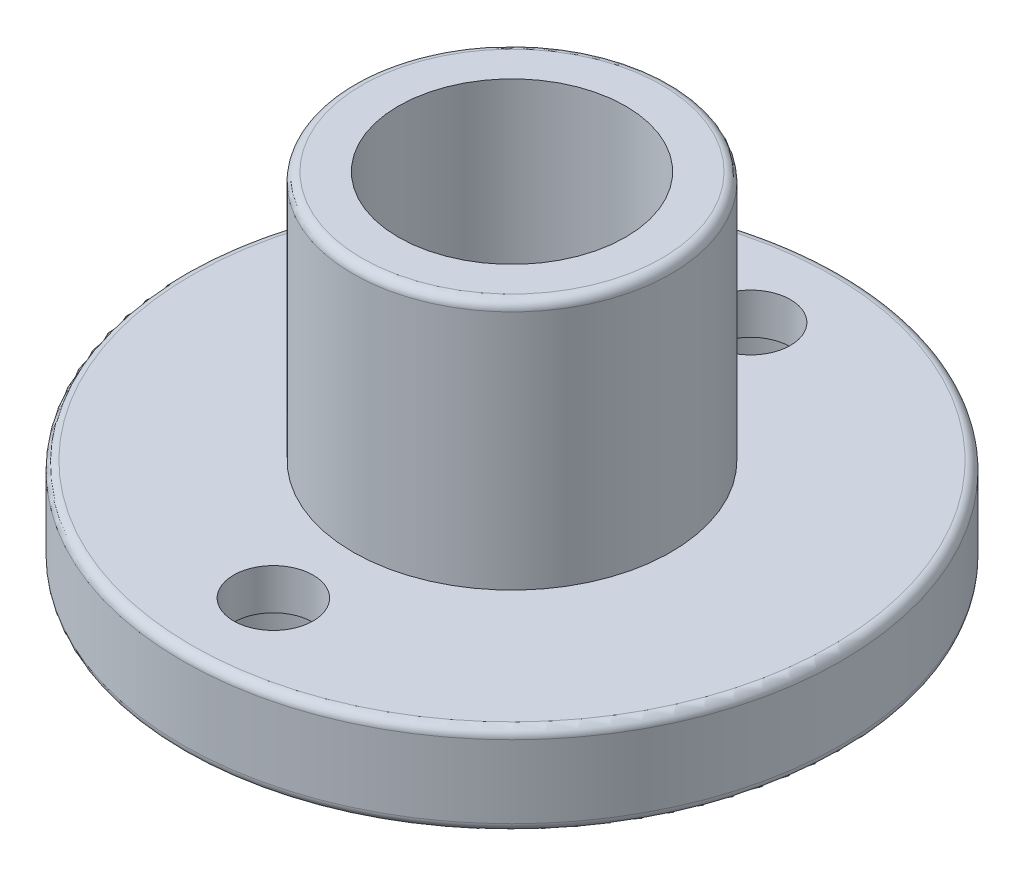
SolidWorks part; units mm, degrees
material "黄铜"
ref_plane "前视基准面" through (0, 0, 0) normal (0, 0, 1) x (1, 0, 0)
ref_plane "上视基准面" through (0, 0, 0) normal (0, 1, 0) x (1, 0, 0)
ref_plane "右视基准面" through (0, 0, 0) normal (1, 0, 0) x (0, 0, -1)
sketch "草图1" plane through (0, 0, 0) normal (0, 1, 0) x (1, 0, 0)
  circle A0 centre (0, 0) radius 14.5
  circle A1 centre (0, 0) radius 7
  circle A2 centre (0, 0) radius 5
  dimension "D1" = 10
  dimension "D2" = 14
  dimension "D3" = 29
extrude "凸台-拉伸1" add sketch "草图1" along normal blind 4 contours A0 A1 region at (-14.0899, 0, 0)
extrude "凸台-拉伸2" add sketch "草图1<3>" along normal blind 15 contours A1 A2 region at (-6.802, 0, 0)
sketch "草图1<3>" plane through (0, 0, 0) normal (0, 1, 0) x (1, 0, 0) same geometry as "草图1"
sketch "草图2" plane through (0, 0, 0) normal (0, -1, 0) x (1, 0, 0)
  circle A0 centre (0, 0) radius 10.5 construction
  circle A1 centre (0, 10.5) radius 3
  circle A2 centre (0, 10.5) radius 1.75
  circle A3 centre (0, -10.5) radius 3
  circle A4 centre (0, -10.5) radius 1.75
  point P12 (0.0296, 0)
  dimension "D1" = 21
  dimension "D2" = 6
  dimension "D3" = 3.5
  dimension "D4" = 2
extrude "切除-拉伸1" cut sketch "草图2" against normal blind 2.2 contours A1 A2 | A3 A4 region at (-2.9151, 0, 10.5) region at (-2.9151, 0, -10.5)
extrude "切除-拉伸2" cut sketch "草图2<4>" against normal through all contours A2 | A4 region at (0, 0, 10.5) region at (0, 0, -10.5)
sketch "草图2<4>" plane through (0, 0, 0) normal (0, -1, 0) x (1, 0, 0) same geometry as "草图2"
fillet "圆角1" radius 0.4 3 edges at (0, 0, 14.5) (0, 4, 14.5) (0, 15, 7)
other "冻结***"
